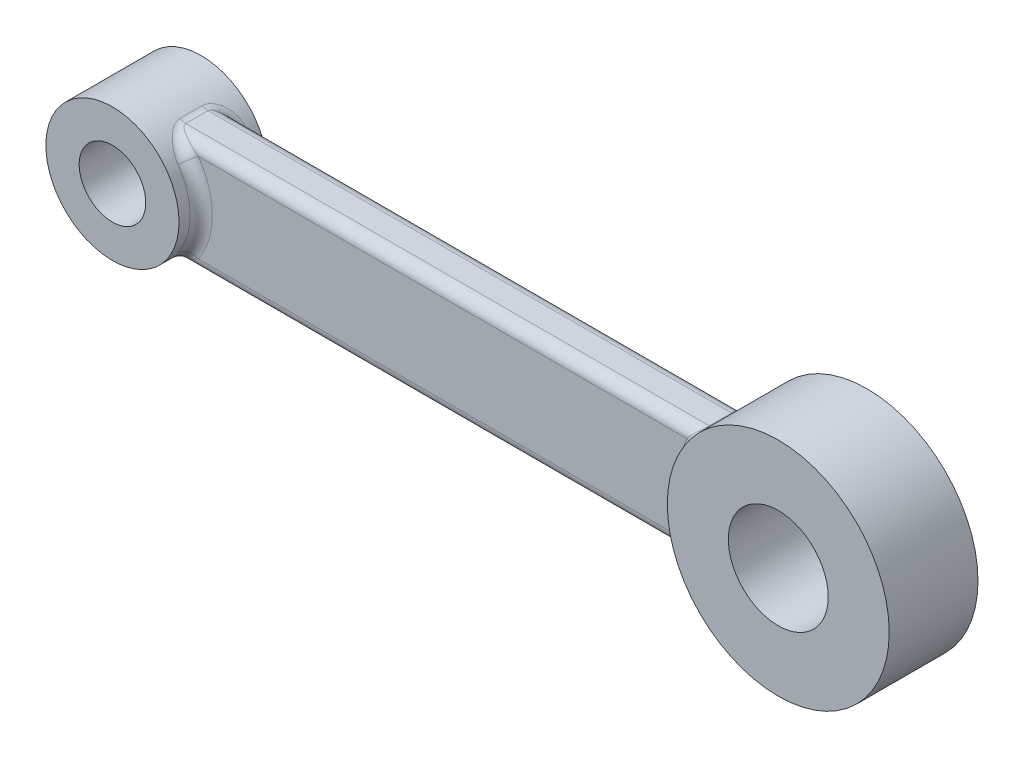
SolidWorks part; units mm, degrees
ref_plane "Front Plane" through (0, 0, 0) normal (0, 0, 1) x (1, 0, 0)
ref_plane "Top Plane" through (0, 0, 0) normal (0, 1, 0) x (1, 0, 0)
ref_plane "Right Plane" through (0, 0, 0) normal (1, 0, 0) x (0, 0, -1)
sketch "Sketch1" plane through (0, 0, 0) normal (0, 0, 1) x (1, 0, 0)
  line L1 (-15, -2.5) -> (15, -2.5)
  line L2 (-15, -2.5) -> (-15, 2.5)
  line L3 (-15, 2.5) -> (15, 2.5)
  line L4 (15, -2.5) -> (15, 2.5)
  line L5 (-15, -2.5) -> (15, 2.5) construction
  line L6 (-15, 2.5) -> (15, -2.5) construction
  point P0 (0, 0)
  dimension "D1" = 30
  dimension "D2" = 5
extrude "Boss-Extrude1" add sketch "Sketch1" along normal mid plane 2
sketch "Sketch3" plane through (0, 0, 0) normal (0, 0, 1) x (1, 0, 0)
  line L0 (-21.701, 0) -> (21.701, 0) construction
  circle A0 centre (-15, 0) radius 3
  circle A1 centre (15, 0) radius 5
  point P4 (0, 0)
  point P8 (0, 0)
  dimension "D1" = 30
  dimension "D2" = 10
  dimension "D3" = 6
  dimension "D4" = 15
extrude "Boss-Extrude3" add sketch "Sketch3" along normal mid plane 4
sketch "Sketch4" plane through (0, 0, 2) normal (0, 0, 1) x (1, 0, 0)
  circle A0 centre (-15, 0) radius 1.5
  dimension "D1" = 3
extrude "Cut-Extrude1" cut sketch "Sketch4" against normal through all
sketch "Sketch6" plane through (0, 0, 2) normal (0, 0, 1) x (1, 0, 0)
  circle A0 centre (15, 0) radius 2.25
  dimension "D1" = 4.5
extrude "Cut-Extrude2" cut sketch "Sketch6" against normal through all
fillet "Fillet1" radius 0.5 2 edges at (-1.3359, -2.5, -1) (-1.3359, -2.5, 1)
fillet "Fillet2" radius 0.5 2 edges at (-1.3359, 2.5, 1) (-1.3359, 2.5, -1)
fillet "Fillet3" radius 0.5 8 edges at (-13.2762, 2.4553, -0.7066) (-13.3417, 2.5, 0) (-13.1981, 2.3986, 0.8019) (-13.2762, -2.4553, 0.7066) (-12, 0, 1) (-13.3417, -2.5, 0) (-13.1981, -2.3986, -0.8019) (-12, 0, -1)
fillet "Fillet4" radius 0.5 8 edges at (10.5801, 2.3376, -0.8688) (10.6699, 2.5, 0) (10.6204, 2.4123, 0.7829) (10, 0, 1) (10.5801, -2.3376, 0.8688) (10.6699, -2.5, 0) (10.6204, -2.4123, -0.7829) (10, 0, -1)
